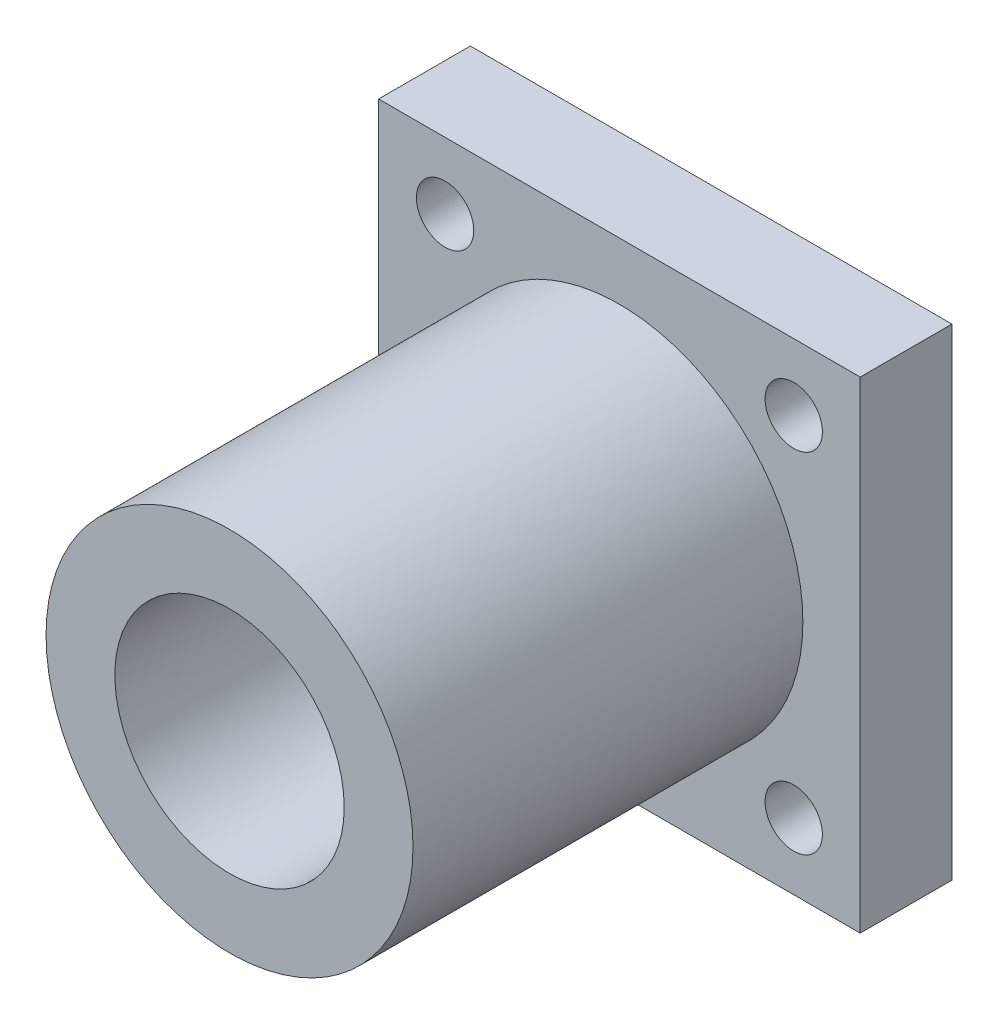
SolidWorks part; units mm, degrees
ref_plane "前视基准面" through (0, 0, 0) normal (0, 0, 1) x (1, 0, 0)
ref_plane "上视基准面" through (0, 0, 0) normal (0, 1, 0) x (1, 0, 0)
ref_plane "右视基准面" through (0, 0, 0) normal (1, 0, 0) x (0, 0, -1)
sketch "草图1" plane through (0, 0, 0) normal (0, 0, 1) x (1, 0, 0)
  line L1 (21, -21) -> (-21, -21)
  line L2 (21, -21) -> (21, 21)
  line L3 (21, 21) -> (-21, 21)
  line L4 (-21, -21) -> (-21, 21)
  line L5 (21, -21) -> (-21, 21) construction
  line L6 (21, 21) -> (-21, -21) construction
  line L7 (15.2028, -15.2028) -> (-15.2028, -15.2028) construction
  line L8 (15.2028, -15.2028) -> (15.2028, 15.2028) construction
  line L9 (15.2028, 15.2028) -> (-15.2028, 15.2028) construction
  line L10 (-15.2028, -15.2028) -> (-15.2028, 15.2028) construction
  line L11 (15.2028, -15.2028) -> (-15.2028, 15.2028) construction
  line L12 (15.2028, 15.2028) -> (-15.2028, -15.2028) construction
  circle A0 centre (0, 0) radius 16
  circle A1 centre (0, 0) radius 10
  circle A2 centre (-15.2028, 15.2028) radius 2.5
  circle A3 centre (15.2028, 15.2028) radius 2.5
  circle A4 centre (15.2028, -15.2028) radius 2.5
  circle A5 centre (-15.2028, -15.2028) radius 2.5
  point P0 (0, 0)
  point P6 (0, 0)
  dimension "D1" = 20
  dimension "D2" = 32
  dimension "D5" = 5
  dimension "D3" = 42
  dimension "D4" = 43
extrude "凸台-拉伸1" add sketch "草图1" along normal blind 8 contours L4 L1 L2 L3 A5 A4 A3 A2 A0 | A0 A1 region at (0, -20.406, 0) region at (-15.5475, 0, 0)
extrude "凸台-拉伸2" add sketch "草图1<3>" along normal blind 42 contours A0 A1 region at (-15.5475, 0, 0)
sketch "草图1<3>" plane through (0, 0, 0) normal (0, 0, 1) x (1, 0, 0) same geometry as "草图1"
